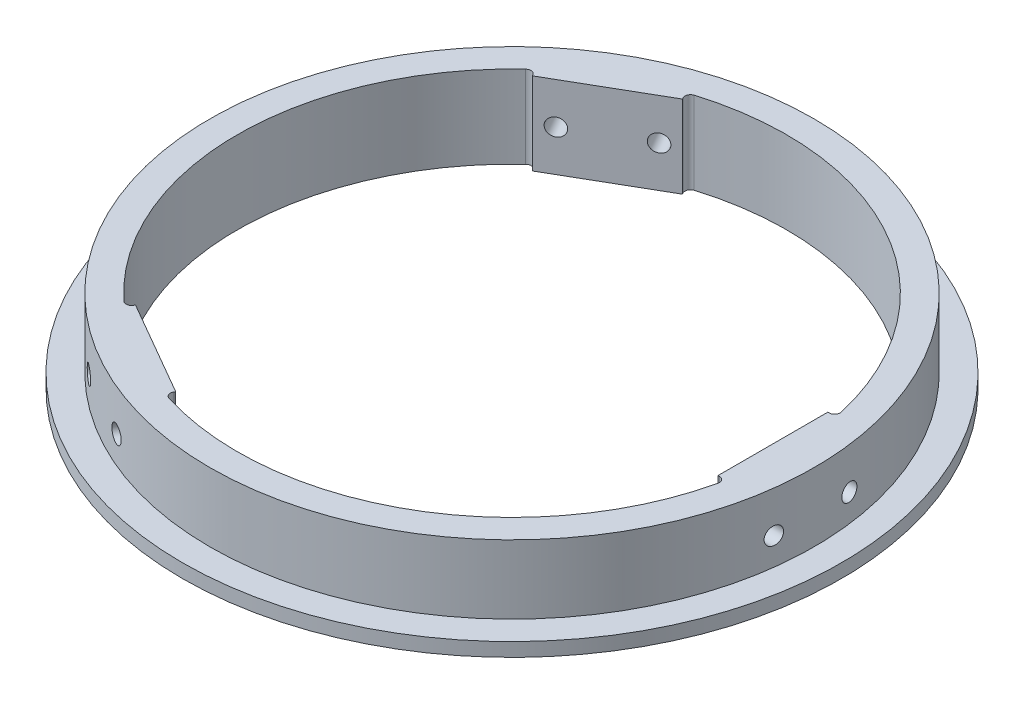
SolidWorks part; units mm, degrees
ref_plane "Front Plane" through (0, 0, 0) normal (0, 0, 1) x (1, 0, 0)
ref_plane "Top Plane" through (0, 0, 0) normal (0, 1, 0) x (1, 0, 0)
ref_plane "Right Plane" through (0, 0, 0) normal (1, 0, 0) x (0, 0, -1)
sketch "Sketch1" plane through (0, 0, 0) normal (0, 1, 0) x (1, 0, 0)
  circle A0 centre (0, 0) radius 152.4
  circle A1 centre (0, 0) radius 127
  dimension "D1" = 304.8
  dimension "D2" = 254
extrude "Boss-Extrude1" add sketch "Sketch1" along normal blind 38.1
sketch "Sketch2" plane through (0, 38.1, 0) normal (0, 1, 0) x (1, 0, 0)
  circle A0 centre (0, 0) radius 139.7
  circle A1 centre (0, 0) radius 152.4 construction
  circle A2 centre (0, 0) radius 152.4
  dimension "D1" = 279.4
extrude "Cut-Extrude1" cut sketch "Sketch2" against normal blind 31.75
sketch "Sketch3" plane through (0, 38.1, 0) normal (0, 1, 0) x (1, 0, 0)
  line L0 (120.65, 25.4) -> (120.65, -25.4)
  line L1 (120.65, 25.4) -> (124.4341, 25.4)
  line L2 (120.65, -25.4) -> (124.4341, -25.4)
  circle A0 centre (0, 0) radius 127 construction
  arc A1 (124.4341, -25.4) -> (124.4341, 25.4) centre (0, 0) ccw
  point P2 (120.65, 0)
  point P7 (118.0601, -24.6185)
  dimension "D1" = 50.8
  dimension "D2" = 120.65
extrude "Boss-Extrude2" add sketch "Sketch3" against normal through all
fillet "Fillet1" radius 2.54 2 edges at (124.4341, 19.05, -25.4) (124.4341, 19.05, 25.4)
pattern_circular "CirPattern1" count 3 over 360 about axis through (0, 38.1, 0) along (0, 1, 0) of "Boss-Extrude2", "Fillet1"
hole_wizard "Hole1" positions "Sketch4" profile "Sketch5" legacy end condition through all
sketch "Sketch4" plane through (120.65, 0, -417.9439) normal (-1, 0, 0) x (0, 0, 1)
  line L0 (400.4814, 19.05) -> (435.4064, 19.05)
  line L3 (326.1579, 0) -> (326.1579, 38.1) construction
  line L6 (392.5439, 0) -> (443.3439, 0) construction
  line L7 (417.9439, 19.05) -> (417.9439, 0)
  point P0 (400.4814, 19.05)
  point P2 (435.4064, 19.05)
  point P19 (326.1579, 19.05)
  dimension "D1" = 34.925
sketch "Sketch5" plane through (120.65, 19.05, -17.4625) normal (0, 1, 0) x (0, 0, 1)
  line L0 (0, 0) -> (0, 87.5323)
  line L1 (0, 87.5323) -> (4, 87.5323)
  line L2 (4, 87.5323) -> (4, 0)
  line L3 (4, 0) -> (0, 0)
  line L4 (0, 110) -> (0, -10) construction
  dimension "Diameter" = 8
  dimension "Depth" = 87.5323
pattern_circular "CirPattern2" count 3 over 360 about axis through (0, 38.1, 0) along (0, 1, 0) of "Hole1"
